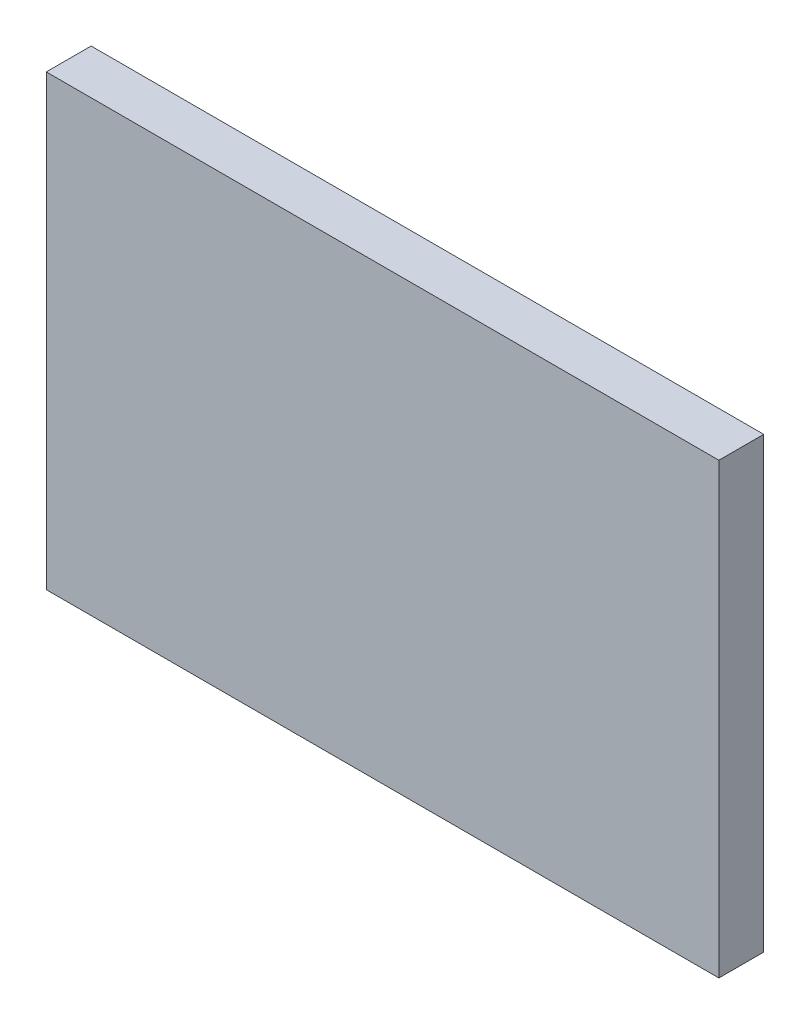
SolidWorks part; units mm, degrees
ref_plane "Ebene vorne" through (0, 0, 0) normal (0, 0, 1) x (1, 0, 0)
ref_plane "Ebene oben" through (0, 0, 0) normal (0, 1, 0) x (1, 0, 0)
ref_plane "Ebene rechts" through (0, 0, 0) normal (1, 0, 0) x (0, 0, -1)
sketch "Skizze1" plane through (0, 0, 0) normal (0, 0, 1) x (1, 0, 0)
  line L0 (0, 0) -> (0, 20)
  line L1 (0, 20) -> (30, 20)
  line L2 (30, 20) -> (30, 0)
  line L3 (30, 0) -> (0, 0)
  dimension "D1" = 30
  dimension "D2" = 20
  dimension "D3" = 20
  dimension "D4" = 90
  dimension "D5" = 90
extrude "Aufsatz-Linear austragen1" add sketch "Skizze1" along normal blind 2
sketch "Skizze4" plane through (0, 0, 0) normal (0, 0, 1) x (1, 0, 0)
  line L1 (0, 0) -> (30, 0)
  line L2 (0, 0) -> (0, 20)
  line L3 (0, 20) -> (30, 20)
  line L4 (30, 0) -> (30, 20)
  dimension "D1" = 30
  dimension "D2" = 20
sketch "Skizze2" plane through (0, 0, 2) normal (0, 0, 1) x (1, 0, 0)
  circle A0 centre (15, 10) radius 18.0278
sketch "Skizze3" plane through (0, 0, 2) normal (0, 0, 1) x (1, 0, 0)
  line L0 (1, 1) -> (29, 1)
  line L1 (1, 1) -> (1, 19)
  line L2 (29, 1) -> (29, 19)
  line L3 (1, 19) -> (29, 19)
  line L4 (1, 1) -> (29, 19) construction
  line L5 (29, 1) -> (1, 19) construction
  line L6 (30, 0) -> (30, 20) construction
  line L7 (30, 20) -> (0, 20) construction
  point P1 (15, 10)
  point P8 (30, 10)
  point P11 (15, 20)
  dimension "D1" = 18
  dimension "D2" = 28
ref_point "SWASI_Vision_Point_1"
ref_point "SWASI_Vision_Point_1_helper"
ref_point "SWASI_Vision_Point_2"
ref_point "SWASI_Vision_Point_2_helper"
ref_point "SWASI_Vision_Point_3"
ref_point "SWASI_Vision_Point_3_helper"
ref_point "SWASI_Vision_Point_4"
ref_plane "SWASI_Alignment_Plane_1" through (0, 0, 0) normal (0, -1, 0) x (-1, 0, 0)
ref_plane "SWASI_Alignment_Plane_2" through (0, 0, 2) normal (0, 0, -1) x (-1, 0, 0)
ref_axis "Achse3" through (0, 0, 2) along (0.9978, 0, -0.0665)
ref_axis "Achse4" through (0, 0, 0) along (0.9978, 0, 0.0665)
ref_point "SWASI_Surface_Center_Point"
ref_axis "SWASI_Norm_Alignment_Plane_3" through (30, 0, 0) along (-1, 0, 0)
ref_plane "SWASI_Alignment_Plane_3_G" through (15, 0, 1) normal (-1, 0, 0) x (0, 0, 1)
